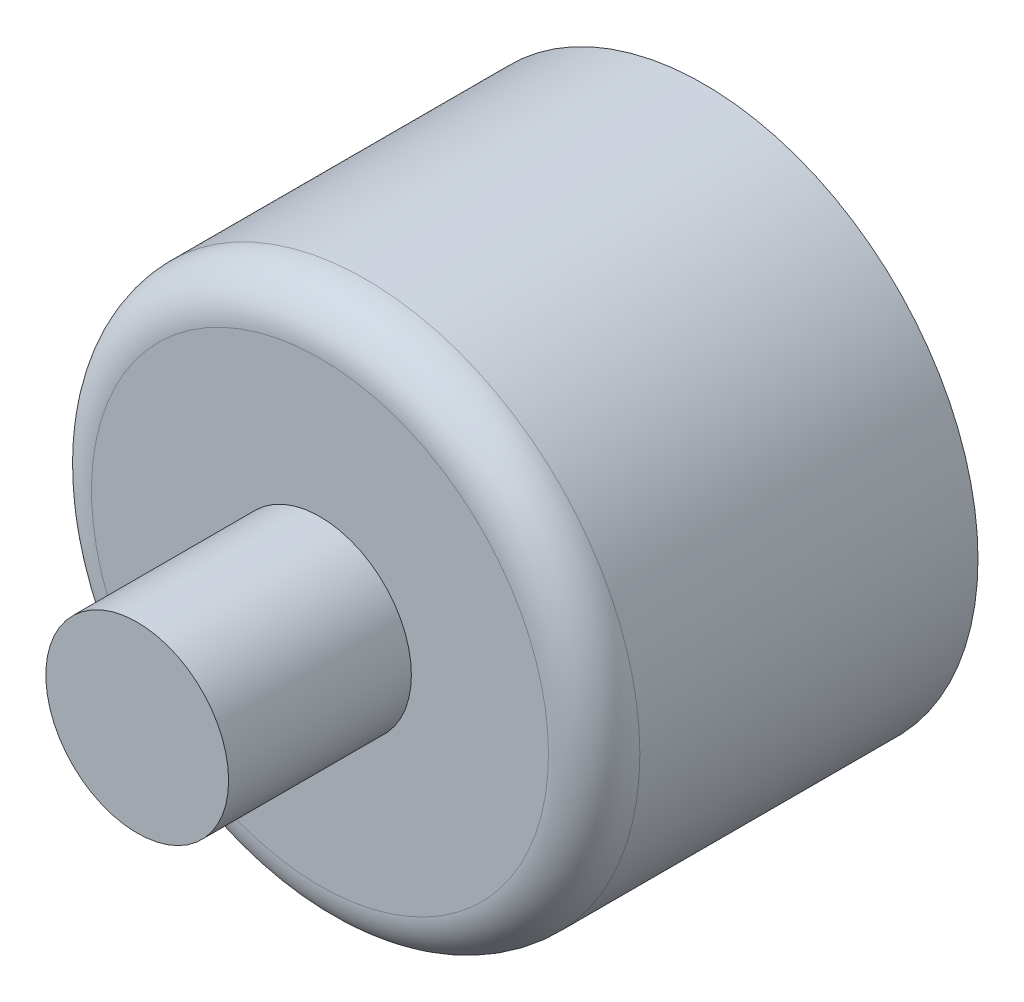
SolidWorks part; units mm, degrees
material "6061-T6 (SS)"
ref_plane "Front Plane" through (0, 0, 0) normal (0, 0, 1) x (1, 0, 0)
ref_plane "Top Plane" through (0, 0, 0) normal (0, 1, 0) x (1, 0, 0)
ref_plane "Right Plane" through (0, 0, 0) normal (1, 0, 0) x (0, 0, -1)
sketch "Sketch1" plane through (0, 0, 0) normal (0, 0, 1) x (1, 0, 0)
  circle A0 centre (0, 0) radius 30
  dimension "D1" = 60
extrude "Boss-Extrude1" add sketch "Sketch1" along normal blind 42
sketch "Sketch3" plane through (0, 0, 42) normal (0, 0, 1) x (1, 0, 0)
  circle A0 centre (0, 0) radius 10
  dimension "D1" = 20
extrude "Boss-Extrude2" add sketch "Sketch3" along normal blind 20
fillet "Fillet1" radius 5 1 edges at (30, 0, 42)
ref_plane "Plane1" through (0, -30, 0) normal (0, 1, 0) x (1, 0, 0)
ref_axis "Axis1" through (0, 0, 37) along (0, 0, -1)
sketch "Sketch9" plane through (0, -30, 0) normal (0, 1, 0) x (1, 0, 0)
  line L0 (-2.642, -20.716) -> (2.642, -20.716) construction
  line L1 (0, -37) -> (0, 0) construction
  line L2 (-2.642, -19.1401) -> (2.642, -19.1401)
  line L3 (-2.642, -22.292) -> (2.642, -22.292)
  arc A0 (-2.642, -19.1401) -> (-2.642, -22.292) centre (-2.642, -20.716) ccw
  arc A1 (2.642, -22.292) -> (2.642, -19.1401) centre (2.642, -20.716) ccw
  point P4 (0, -20.716)
extrude "Boss-Extrude6" add sketch "Sketch9" against normal blind 2 separate body
